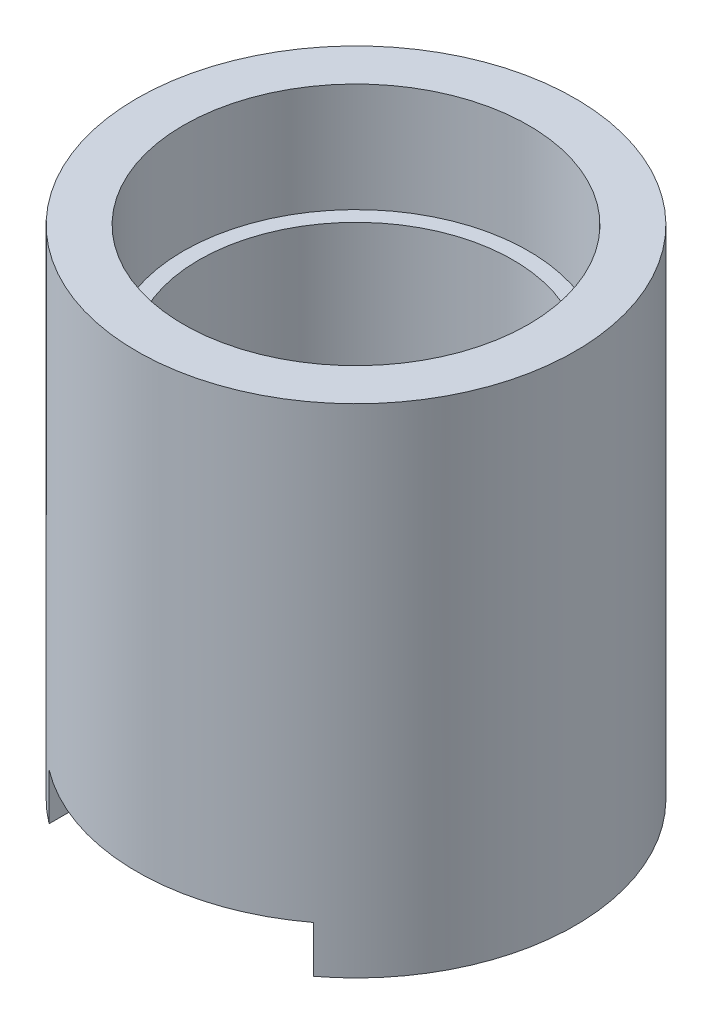
SolidWorks part; units mm, degrees
ref_plane "Plan de face" through (0, 0, 0) normal (0, 0, 1) x (1, 0, 0)
ref_plane "Plan de dessus" through (0, 0, 0) normal (0, 1, 0) x (1, 0, 0)
ref_plane "Plan de droite" through (0, 0, 0) normal (1, 0, 0) x (0, 0, -1)
sketch "Esquisse1" plane through (0, 0, 0) normal (0, 0, 1) x (1, 0, 0)
  line L0 (-1.85, 0) -> (-1.85, 10)
  line L1 (-1.85, 10) -> (-10.1, 10)
  line L2 (-10.1, 10) -> (-10.1, 25)
  line L3 (-10.1, 25) -> (-11.1, 25)
  line L4 (-11.1, 25) -> (-11.1, 32)
  line L5 (-11.1, 32) -> (-14.1, 32)
  line L6 (-14.1, 32) -> (-14.1, 0)
  line L7 (-14.1, 0) -> (-1.85, 0)
  line L8 (0, 0) -> (0, -3.854) construction
  dimension "D1" = 1.85
  dimension "D2" = 10
  dimension "D3" = 11.1
  dimension "D4" = 3
  dimension "D5" = 7
  dimension "D6" = 15
  dimension "D7" = 1
revolve "Révolution1" add sketch "Esquisse1" angle 360 about L8
sketch "Esquisse2" plane through (0, 0, 0) normal (0, 0, 1) x (1, 0, 0)
  line L0 (-14.1, 0) -> (14.1, 0) construction
  line L1 (-8.5, 0) -> (8.5, 0)
  line L2 (-8.5, 0) -> (-8.5, 3)
  line L3 (-8.5, 3) -> (8.5, 3)
  line L4 (8.5, 0) -> (8.5, 3)
  point P6 (0, 3)
  dimension "D1" = 17
  dimension "D2" = 3
extrude "Enlèv. mat.-Extru.1" cut sketch "Esquisse2" against normal through all and the other way through all
chamfer "Chanfrein1" distance 0.5 angle 45 1 edges at (-1.85, 3, 0)
thread "Filetage1" pitch 0.7 method cut trim with start face yes trim with end face yes profile "Profil de filetage1" start angle 0, offset 1, length 0, pitch 0.7, diameter 3.7
ref_plane "Plan1" through (1.85, 2, 0) normal (0, 0, 1) x (1, 0, 0)
sketch "Profil de filetage1" plane through (1.85, 2, 0) normal (0, 0, 1) x (1, 0, 0)
  line L0 (0, 0) -> (0, 0.7) construction
  line L1 (0, 0) -> (0.3789, 0.2187)
  line L2 (0.3789, 0.2187) -> (0.3789, 0.3062)
  line L3 (0.3789, 0.3062) -> (0, 0.525)
  line L4 (0.3789, 0.2625) -> (0, 0.2625) construction
  line L11 (0, 0) -> (0, 0.525)
  point P2 (0, 0)
  dimension "Pitch" = 0.7
  dimension "Profile_Angle" = 60
  dimension "Profile_Land" = 0.0875
  dimension "Profile_Height" = 0.3789
